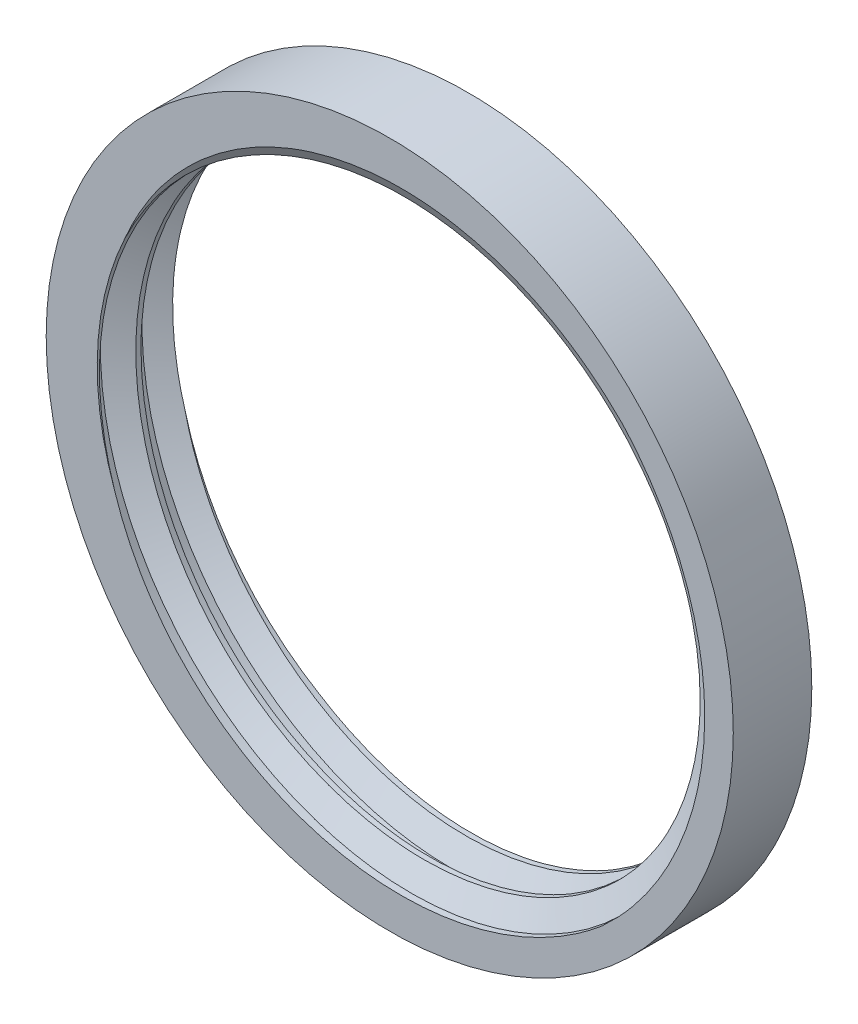
SolidWorks part; units mm, degrees
ref_plane "Plano frontal" through (0, 0, 0) normal (0, 0, 1) x (1, 0, 0)
ref_plane "Plano superior" through (0, 0, 0) normal (0, 1, 0) x (1, 0, 0)
ref_plane "Plano direito" through (0, 0, 0) normal (1, 0, 0) x (0, 0, -1)
sketch "Esboço1" plane through (0, 0, 0) normal (0, 0, 1) x (1, 0, 0)
  circle A0 centre (0, 0) radius 26.25
  circle A1 centre (0, 0) radius 22.35
  dimension "D1" = 44.7
  dimension "D2" = 52.5
extrude "Ressalto-extrusão1" add sketch "Esboço1" along normal blind 6
thread "Rosca1" pitch 3.175 method cut profile "Perfil da rosca1" start angle 0, offset 3, length 25, pitch 3.175, diameter 44.7
ref_plane "Plano1" through (-22.35, 0, 9) normal (0, 1, 0) x (1, 0, 0)
sketch "Perfil da rosca1" plane through (-22.35, 0, 9) normal (0, 1, 0) x (1, 0, 0)
  line L0 (0, 0) -> (0, 3.175) construction
  line L11 (0, 0) -> (0, 2.7781)
  line L12 (0, 2.7781) -> (-1.7185, 1.7859)
  line L13 (-1.7185, 1.7859) -> (-1.7185, 0.9922)
  line L15 (-1.7185, 0.9922) -> (0, 0)
  line L17 (-1.7185, 1.3891) -> (0, 1.3891) construction
  point P2 (0, 0)
  dimension "Pitch" = 3.175
  dimension "Profile_Angle" = 60
  dimension "Profile_Land" = 0.7937
  dimension "Profile_Height" = 1.7185
